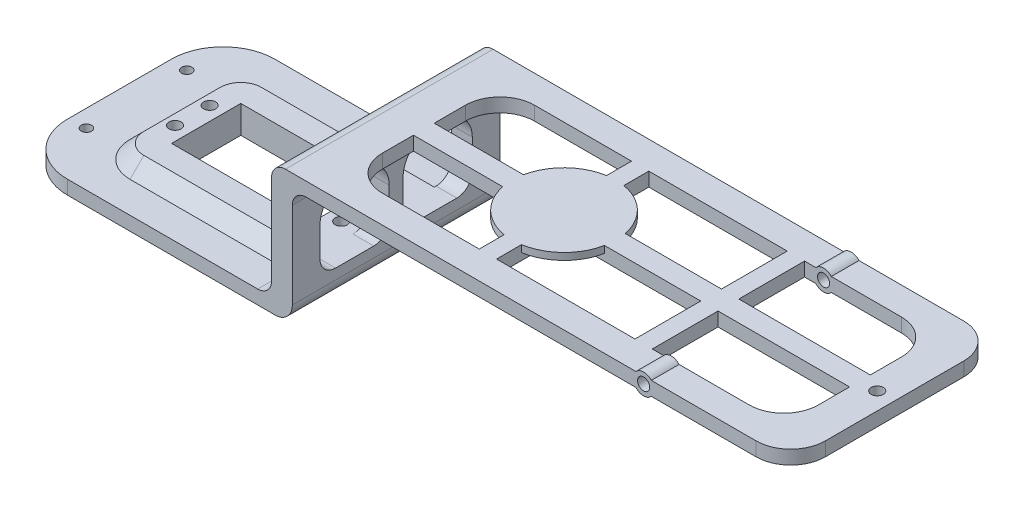
SolidWorks part; units mm, degrees
ref_plane "Ön Düzlem" through (0, 0, 0) normal (0, 0, 1) x (1, 0, 0)
ref_plane "Üst Düzlem" through (0, 0, 0) normal (0, 1, 0) x (1, 0, 0)
ref_plane "Sağ Düzlem" through (0, 0, 0) normal (1, 0, 0) x (0, 0, -1)
sketch "Çizim1" plane through (0, 0, 0) normal (0, 0, 1) x (1, 0, 0)
  line L0 (0, 0) -> (80, 0)
  line L1 (80, 0) -> (80, 30)
  line L2 (84, 34) -> (224, 34)
  line L3 (224, 34) -> (224, 38)
  line L4 (224, 38) -> (78, 38)
  line L5 (74, 34) -> (74, 4)
  line L6 (74, 4) -> (0, 4)
  line L7 (0, 4) -> (0, 0)
  arc A0 (74, 34) -> (78, 38) centre (78, 34) cw
  arc A1 (80, 30) -> (84, 34) centre (84, 30) cw
  point P11 (74, 38)
  dimension "D7" = 4
  dimension "D1" = 4
  dimension "D2" = 80
  dimension "D3" = 6
  dimension "D4" = 30
  dimension "D5" = 4
  dimension "D6" = 150
extrude "Yükseklik-Ekstrüzyon1" add sketch "Çizim1" along normal blind 60
sketch "Çizim2" plane through (74, 0, 0) normal (-1, 0, 0) x (0, 0, 1)
  line L0 (30, 34) -> (30, 4) construction
  line L1 (60, 34) -> (0, 34) construction
  line L2 (60, 4) -> (0, 4) construction
  line L3 (0, 34) -> (0, 4) construction
  line L4 (16, 29) -> (20, 29)
  line L5 (8, 21) -> (8, 12.4825)
  line L6 (12.4825, 8) -> (23.5175, 8)
  line L7 (28, 21) -> (28, 12.4825)
  line L8 (32, 21) -> (32, 12.4825)
  line L9 (47.5175, 8) -> (36.4825, 8)
  line L10 (52, 21) -> (52, 12.4825)
  line L11 (44, 29) -> (40, 29)
  arc A0 (44, 29) -> (52, 21) centre (44, 21) cw
  arc A1 (40, 29) -> (32, 21) centre (40, 21) ccw
  arc A2 (28, 21) -> (20, 29) centre (20, 21) ccw
  arc A3 (8, 21) -> (16, 29) centre (16, 21) cw
  arc A4 (47.5175, 8) -> (52, 12.4825) centre (47.5175, 12.4825) ccw
  arc A5 (36.4825, 8) -> (32, 12.4825) centre (36.4825, 12.4825) cw
  arc A6 (23.5175, 8) -> (28, 12.4825) centre (23.5175, 12.4825) ccw
  arc A7 (12.4825, 8) -> (8, 12.4825) centre (12.4825, 12.4825) cw
  point P18 (52, 29)
  point P21 (32, 29)
  point P24 (28, 29)
  point P27 (8, 29)
  point P30 (52, 8)
  point P33 (32, 8)
  point P36 (28, 8)
  point P39 (8, 8)
  dimension "D5" = 8
  dimension "D6" = 4.4825
  dimension "D1" = 5
  dimension "D2" = 4
  dimension "D3" = 8
  dimension "D4" = 4
extrude "Kes-Ekstrüzyon1" cut sketch "Çizim2" against normal blind 60
sketch "Çizim3" plane through (0, 4, 0) normal (0, 1, 0) x (1, 0, 0)
  line L0 (0, -30) -> (78, -30) construction
  line L1 (0, -60) -> (0, 0) construction
  line L2 (78, -60) -> (78, 0) construction
  circle A0 centre (5, -15.5) radius 1.5
  circle A1 centre (5, -44.5) radius 1.5
  circle A2 centre (65, -15.5) radius 1.5
  circle A3 centre (65, -44.5) radius 1.5
  dimension "D4" = 3
  dimension "D5" = 3
  dimension "D6" = 3
  dimension "D7" = 3
  dimension "D1" = 29
  dimension "D2" = 60
  dimension "D3" = 5
extrude "Kes-Ekstrüzyon2" cut sketch "Çizim3" against normal blind 60
fillet "Radyus1" radius 15 2 edges at (0, 2, 60) (0, 2, 0)
fillet "Radyus2" radius 5 1 edges at (80, 0, 30)
sketch "Çizim4" plane through (0, 4, 0) normal (0, 1, 0) x (1, 0, 0)
  line L0 (0, -30) -> (78, -30) construction
  line L1 (25.11, -20) -> (65.11, -20)
  line L2 (25.11, -20) -> (25.11, -40)
  line L3 (25.11, -40) -> (65.11, -40)
  line L4 (65.11, -20) -> (65.11, -40)
  line L5 (0, -45) -> (0, -15) construction
  line L6 (78, -60) -> (78, 0) construction
  circle A0 centre (21.11, -25) radius 1.75
  circle A1 centre (21.11, -35) radius 1.75
  circle A2 centre (69.11, -25) radius 1.75
  circle A3 centre (69.11, -35) radius 1.75
  dimension "D5" = 3.5
  dimension "D6" = 3.5
  dimension "D9" = 3.5
  dimension "D10" = 3.5
  dimension "D1" = 25.11
  dimension "D2" = 20
  dimension "D3" = 40
  dimension "D4" = 10
  dimension "D7" = 4
  dimension "D8" = 4
extrude "Kes-Ekstrüzyon3" cut sketch "Çizim4" against normal blind 60
sketch "Çizim5" plane through (0, 4, 0) normal (0, 1, 0) x (1, 0, 0)
  line L0 (0, -30) -> (83.3775, -30) construction
  line L1 (24.11, -13) -> (74, -13)
  line L2 (18.11, -19) -> (18.11, -41)
  line L3 (24.11, -47) -> (74, -47)
  line L4 (74, -13) -> (74, -47)
  line L5 (0, -45) -> (0, -15) construction
  line L6 (65.11, -20) -> (25.11, -20) construction
  line L7 (25.11, -20) -> (25.11, -40) construction
  line L10 (74, -60) -> (74, 0) construction
  line L12 (25.11, -20) -> (65.11, -20)
  line L13 (25.11, -20) -> (25.11, -40)
  line L14 (25.11, -40) -> (65.11, -40)
  line L15 (65.11, -20) -> (65.11, -40)
  arc A0 (24.11, -47) -> (18.11, -41) centre (24.11, -41) cw
  arc A1 (18.11, -19) -> (24.11, -13) centre (24.11, -19) cw
  circle A2 centre (21.11, -25) radius 1.75
  circle A3 centre (21.11, -35) radius 1.75
  circle A4 centre (65, -44.5) radius 1.5
  circle A5 centre (69.11, -25) radius 1.75
  circle A6 centre (69.11, -35) radius 1.75
  circle A7 centre (65, -15.5) radius 1.5
  dimension "D3" = 6
  dimension "D4" = 3.5
  dimension "D5" = 3.5
  dimension "D6" = 3
  dimension "D7" = 3.5
  dimension "D8" = 3.5
  dimension "D9" = 3
  dimension "D1" = 7
  dimension "D2" = 7
extrude "Yükseklik-Ekstrüzyon2" add sketch "Çizim5" along normal blind 4
chamfer "Pah1" distance 4 angle 45 5 edges at (49.055, 4, 13) (19.8674, 4, 14.7574) (18.11, 4, 30) (19.8674, 4, 45.2426) (49.055, 4, 47)
fillet "Radyus3" radius 4 2 edges at (74, 4, 55.5) (74, 4, 4.5)
sketch "Çizim6" plane through (0, 38, 0) normal (0, 1, 0) x (1, 0, 0)
  line L0 (224, -60) -> (78, -60) construction
  line L1 (204, -52) -> (98, -52)
  line L2 (214, -42) -> (214, -33)
  line L3 (204, -8) -> (98, -8)
  line L4 (88, -42) -> (88, -33)
  line L5 (224, 0) -> (78, 0) construction
  line L6 (78, -60) -> (78, 0) construction
  line L7 (224, -60) -> (224, 0) construction
  line L8 (214, -33) -> (88, -33)
  line L9 (214, -27) -> (88, -27)
  line L10 (214, -30) -> (88, -30) construction
  line L11 (214, -27) -> (214, -18)
  line L12 (88, -27) -> (88, -18)
  arc A0 (98, -8) -> (88, -18) centre (98, -18) ccw
  arc A1 (88, -42) -> (98, -52) centre (98, -42) ccw
  arc A2 (204, -8) -> (214, -18) centre (204, -18) cw
  arc A3 (214, -42) -> (204, -52) centre (204, -42) cw
  dimension "D5" = 10
  dimension "D1" = 8
  dimension "D2" = 8
  dimension "D3" = 10
  dimension "D4" = 10
  dimension "D6" = 6
  dimension "D7" = 9
extrude "Kes-Ekstrüzyon4" cut sketch "Çizim6" against normal blind 4
sketch "Çizim7" plane through (0, 38, 0) normal (0, 1, 0) x (1, 0, 0)
  line L0 (98, -52) -> (204, -52) construction
  line L3 (176, -52) -> (171, -52)
  line L4 (176, -52) -> (176, -33)
  line L5 (176, -33) -> (171, -33)
  line L6 (171, -52) -> (171, -33)
  line L7 (214, -33) -> (88, -33) construction
  line L8 (88, -27) -> (214, -27) construction
  line L9 (131, -52) -> (126, -52)
  line L10 (131, -52) -> (131, -33)
  line L11 (131, -33) -> (126, -33)
  line L12 (126, -52) -> (126, -33)
  line L13 (176, -27) -> (171, -27)
  line L14 (176, -27) -> (176, -8)
  line L15 (176, -8) -> (171, -8)
  line L16 (171, -27) -> (171, -8)
  line L17 (204, -8) -> (98, -8) construction
  line L18 (214, -27) -> (214, -18) construction
  line L19 (131, -27) -> (126, -27)
  line L20 (131, -27) -> (131, -8)
  line L21 (131, -8) -> (126, -8)
  line L22 (126, -27) -> (126, -8)
  line L23 (88, -18) -> (88, -27) construction
  line L24 (214, -42) -> (214, -33) construction
  point P30 (126, -42.5)
  dimension "D1" = 5
  dimension "D2" = 5
  dimension "D3" = 5
  dimension "D4" = 5
  dimension "D5" = 38
  dimension "D6" = 38
  dimension "D7" = 38
  dimension "D8" = 38
extrude "Yükseklik-Ekstrüzyon3" add sketch "Çizim7" against normal up to vertex (4 mm away) up to point (88, 34, 33)
sketch "Çizim8" plane through (0, 38, 0) normal (0, 1, 0) x (1, 0, 0)
  line L0 (131, -33) -> (126, -27) construction
  line L1 (126, -33) -> (131, -27) construction
  circle A0 centre (128.5, -30) radius 15
  dimension "D1" = 30
extrude "Yükseklik-Ekstrüzyon4" add sketch "Çizim8" against normal blind 2
sketch "Çizim9" plane through (0, 0, 60) normal (0, 0, 1) x (1, 0, 0)
  line L0 (224, 36) -> (161.2517, 36) construction
  line L1 (224, 34) -> (224, 38) construction
  circle A0 centre (181.5, 36) radius 2
  circle A1 centre (181.5, 36) radius 3
  dimension "D1" = 4
  dimension "D3" = 6
  dimension "D2" = 42.5
extrude "Yükseklik-Ekstrüzyon5" add sketch "Çizim9" against normal up to vertex (8 mm away) up to point (176, 38, 52)
sketch "Çizim10" plane through (0, 0, 60) normal (0, 0, 1) x (1, 0, 0)
  circle A0 centre (181.5, 36) radius 1.75
  dimension "D1" = 3.5
extrude "Kes-Ekstrüzyon5" cut sketch "Çizim10" against normal blind 10
sketch "Çizim11" plane through (0, 0, 0) normal (0, 0, -1) x (-1, 0, 0)
  circle A0 centre (-181.5, 36) radius 3
  dimension "D1" = 6
extrude "Yükseklik-Ekstrüzyon6" add sketch "Çizim11" against normal up to vertex (8 mm away) up to point (176, 38, 8)
sketch "Çizim12" plane through (0, 0, 0) normal (0, 0, -1) x (-1, 0, 0)
  circle A0 centre (-181.5, 36) radius 1.75
  dimension "D1" = 3.5
extrude "Kes-Ekstrüzyon6" cut sketch "Çizim12" against normal blind 10
sketch "Çizim13" plane through (0, 38, 0) normal (0, 1, 0) x (1, 0, 0)
  line L0 (224, -30) -> (200.9157, -30) construction
  line L1 (224, -60) -> (224, 0) construction
  circle A0 centre (219, -30) radius 1.75
  dimension "D1" = 3.5
  dimension "D2" = 5
extrude "Kes-Ekstrüzyon7" cut sketch "Çizim13" against normal blind 10
fillet "Radyus4" radius 10 2 edges at (224, 36, 0) (224, 36, 60)
